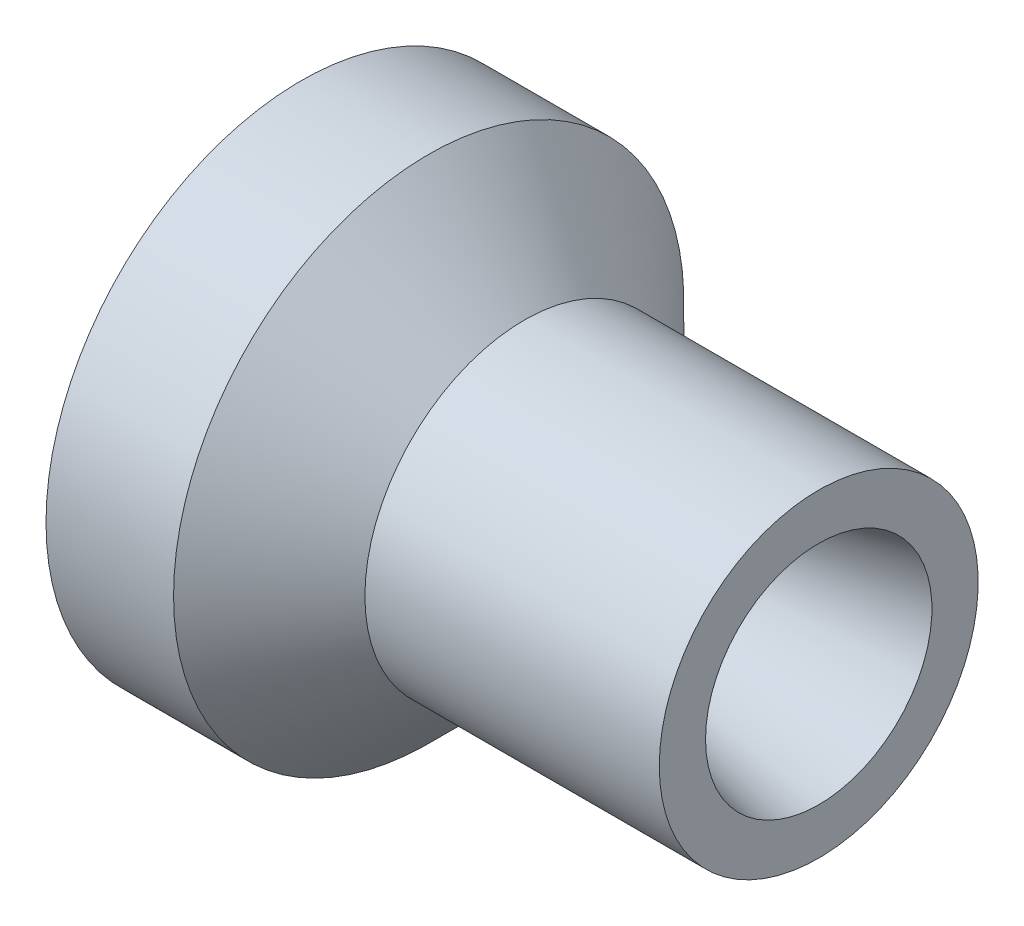
SolidWorks part; units mm, degrees
material "C (Graphite)"
ref_plane "Front Plane" through (0, 0, 0) normal (0, 0, 1) x (1, 0, 0)
ref_plane "Top Plane" through (0, 0, 0) normal (0, 1, 0) x (1, 0, 0)
ref_plane "Right Plane" through (0, 0, 0) normal (1, 0, 0) x (0, 0, -1)
sketch "Sketch1" plane through (0, 0, 0) normal (0, 0, 1) x (1, 0, 0)
  line L0 (0, 0) -> (0, 9.525)
  line L1 (103.0716, 37.7825) -> (46.609, 49.784)
  line L3 (0, 60.325) -> (76.2, 60.325) construction
  line L4 (0, 9.525) -> (40.259, 49.784)
  line L5 (40.259, 49.784) -> (46.609, 49.784)
  line L6 (103.0716, 37.7825) -> (103.0716, 28.575)
  line L7 (25.4, 9.525) -> (0, 9.525)
  line L9 (25.4, 9.525) -> (44.45, 28.575)
  line L12 (44.45, 28.575) -> (103.0716, 28.575)
  dimension "D1" = 60.325
  dimension "D2" = 45
  dimension "D3" = 6.35
  dimension "D4" = 25.4
  dimension "D5" = 9.525
  dimension "D6" = 19.05
  dimension "D7" = 12
  dimension "D8" = 135
  dimension "D9" = 10.541
  dimension "D11" = 58.6216
  dimension "D12" = 22.5425
revolve "Revolve1" add sketch "Sketch1" angle 360 about L3 region at (50.0219, 31.6757, 0)
